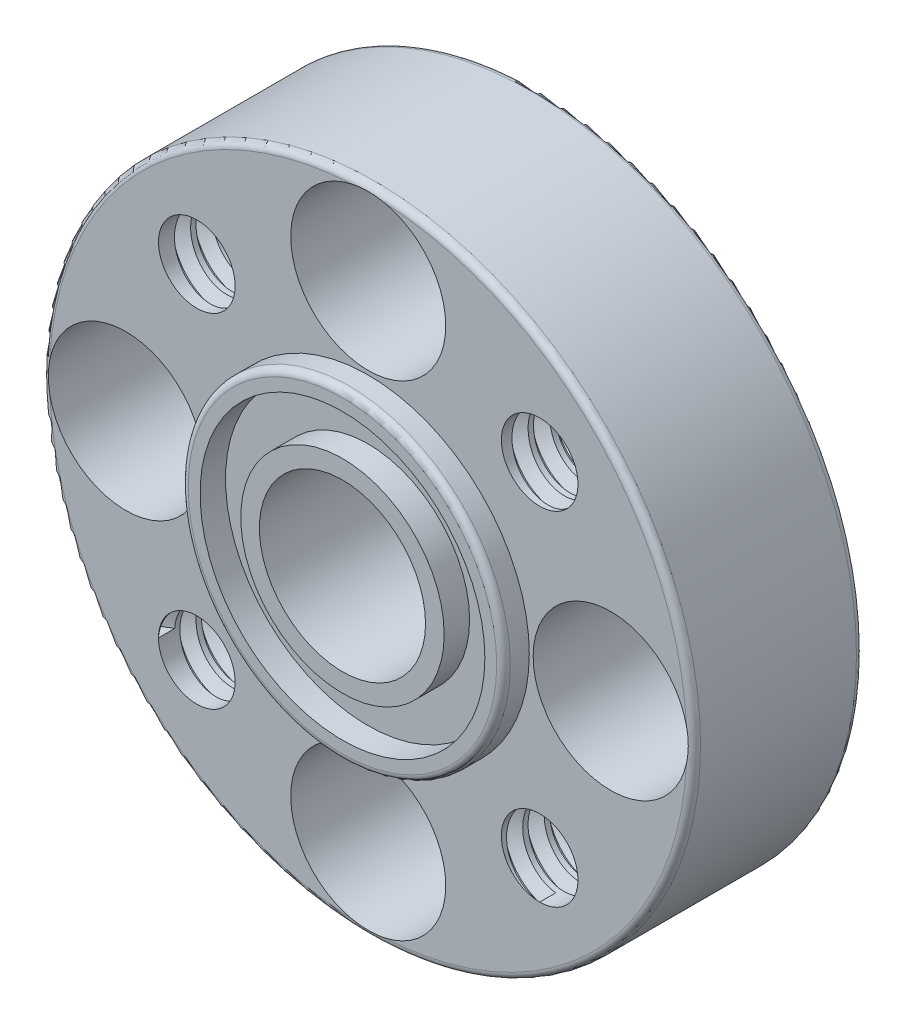
SolidWorks part; units mm, degrees
ref_plane "Front Plane" through (0, 0, 0) normal (0, 0, 1) x (1, 0, 0)
ref_plane "Top Plane" through (0, 0, 0) normal (0, 1, 0) x (1, 0, 0)
ref_plane "Right Plane" through (0, 0, 0) normal (1, 0, 0) x (0, 0, -1)
sketch "Sketch1" plane through (0, 0, 0) normal (0, 0, 1) x (1, 0, 0)
  circle A0 centre (0, 0) radius 9.6
  dimension "D1" = 19.2
extrude "Boss-Extrude1" add sketch "Sketch1" along normal blind 5 contours A0
sketch "Sketch4" plane through (0, 0, 5) normal (0, 0, 1) x (1, 0, 0)
  circle A0 centre (0, 0) radius 4.75
  dimension "D1" = 9.5
extrude "Boss-Extrude4" add sketch "Sketch4" along normal blind 0.76 contours A0
sketch "Sketch5" plane through (0, 0, 5.76) normal (0, 0, 1) x (1, 0, 0)
  circle A0 centre (0, 0) radius 2.45
  dimension "D1" = 4.9
extrude "Cut-Extrude2" cut sketch "Sketch5" against normal through all
sketch "Sketch6" plane through (0, 0, 5.76) normal (0, 0, 1) x (1, 0, 0)
  circle A0 centre (0, 0) radius 3
  circle A1 centre (0, 0) radius 4.2
  dimension "D1" = 8.4
  dimension "D2" = 6
extrude "Cut-Extrude3" cut sketch "Sketch6" against normal blind 0.75
fillet "Fillet1" radius 0.2 3 edges at (4.75, 0, 5.76) (9.6, 0, 0) (9.6, 0, 5)
sketch "Sketch7" plane through (0, 0, 5) normal (0, 0, 1) x (1, 0, 0)
  circle A0 centre (0, -7.15) radius 2.285
  dimension "D1" = 4.57
hole_wizard "CBORE for M2 Hex Socket Head Cap Screw1" positions "3DSketch1" profile "Sketch8" counterbore size "M2" standard "DIN" end condition through all
sketch3d "3DSketch1"
  point P0 (0, -7.15, 5)
sketch "Sketch8" plane through (0, -7.15, 5) normal (1, 0, 0) x (0, -1, 0)
  line L0 (0, 0) -> (0, 5.2282)
  line L1 (0, 5.2282) -> (1.2, 5.2282)
  line L3 (1.2, 5.2282) -> (1.2, 4)
  line L4 (1.2, 4) -> (2.286, 4)
  line L5 (2.286, 4) -> (2.286, 0)
  line L7 (2.286, 0) -> (0, 0)
  line L11 (0, -6.35) -> (0, 107.95) construction
  dimension "Thru Hole Dia." = 2.4
  dimension "Thru Hole Depth" = 5.2282
  dimension "C'Bore Dia." = 4.572
  dimension "C'Bore Depth" = 4
sketch "Sketch9" plane through (0, 0, 5) normal (0, 0, 1) x (1, 0, 0)
  arc A1 (0, -7.15) -> (-5.0558, -5.0558) centre (0, 0) cw construction
  circle A2 centre (-5.0558, -5.0558) radius 1.13
  dimension "D1" = 45
  dimension "D2" = 2.26
extrude "Cut-Extrude4" cut sketch "Sketch9" against normal through all contours A2
thread "Thread1" pitch 0.635 method cut profile "Thread Profile2" start angle 0, offset 0, length 0, pitch 0.635, diameter 2.26
ref_plane "Plane2" through (-6.1858, -5.0558, 5) normal (0, -1, 0) x (-1, 0, 0)
sketch "Thread Profile2" plane through (-6.1858, -5.0558, 5) normal (0, -1, 0) x (-1, 0, 0)
  line L0 (0, 0) -> (0, 0.635) construction
  line L1 (0, 0) -> (0.3437, 0.1984)
  line L2 (0.3437, 0.1984) -> (0.3437, 0.2778)
  line L3 (0.3437, 0.2778) -> (0, 0.4762)
  line L4 (0.3437, 0.2381) -> (0, 0.2381) construction
  line L11 (0, 0) -> (0, 0.4762)
  point P2 (0, 0)
  dimension "Pitch" = 0.635
  dimension "Profile_Angle" = 60
  dimension "Profile_Land" = 0.0794
  dimension "Profile_Height" = 0.3437
sketch "Sketch20" plane through (0, 0, 0) normal (0, 1, 0) x (1, 0, 0)
  line L0 (0, -6.3944) -> (0, 0.7339) construction
pattern_circular "CirPattern1" count 4 every 90 about axis through (0, 0, 6.3944) along (0, 0, -1) of "CBORE for M2 Hex Socket Head Cap Screw1", "Cut-Extrude4", "Thread1"
